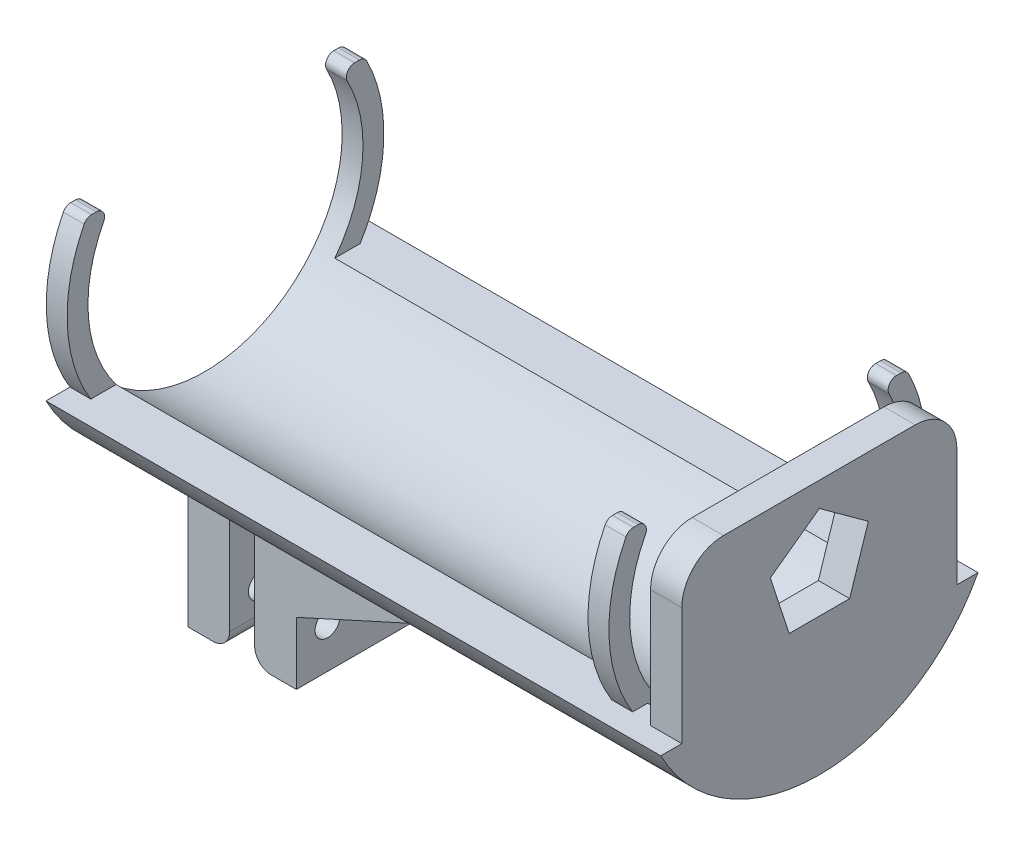
SolidWorks part; units mm, degrees
ref_plane "Front" through (0, 0, 0) normal (0, 0, 1) x (1, 0, 0)
ref_plane "Top" through (0, 0, 0) normal (0, 1, 0) x (1, 0, 0)
ref_plane "Right" through (0, 0, 0) normal (1, 0, 0) x (0, 0, -1)
sketch "Sketch1" plane through (0, 0, 0) normal (1, 0, 0) x (0, 0, -1)
  line L1 (-38.0657, -20) -> (-26.2488, -20)
  line L2 (26.2488, -20) -> (38.0657, -20)
  arc A0 (-26.2488, -20) -> (26.2488, -20) centre (0, 0) ccw
  arc A1 (-38.0657, -20) -> (38.0657, -20) centre (0, 0) ccw
  dimension "D1" = 66
  dimension "D2" = 10
  dimension "D3" = 20
extrude "Boss-Extrude1" add sketch "Sketch1" along normal mid plane 140
sketch "Sketch2" plane through (70, 0, 0) normal (1, 0, 0) x (0, 0, -1)
  line L0 (-33.3354, 18.2414) -> (-27.5, 18.2414)
  line L1 (27.5, 18.2414) -> (33.3354, 18.2414)
  arc A0 (-27.5, 18.2414) -> (27.5, 18.2414) centre (0, 0) ccw
  arc A1 (-33.3354, 18.2414) -> (33.3354, 18.2414) centre (0, 0) ccw
  dimension "D1" = 5
  dimension "D2" = 55
extrude "Boss-Extrude2" add sketch "Sketch2" against normal blind 5 from offset 5 offset against normal yes
sketch "Sketch3" plane through (70, 0, 0) normal (1, 0, 0) x (0, 0, -1)
  line L3 (-27.5, 18.2414) -> (-33.3354, 18.2414) construction
  line L4 (38.0657, -20) -> (26.2488, -20)
  line L5 (-33, -20) -> (-33, 8.2414)
  line L6 (-23, 18.2414) -> (23, 18.2414)
  line L7 (-26.2488, -20) -> (-38.0657, -20)
  line L8 (38.0657, -20) -> (33, -20)
  line L11 (-33, -20) -> (-38.0657, -20)
  line L12 (33.3354, 18.2414) -> (27.5, 18.2414) construction
  line L13 (33, 8.2414) -> (33, -20)
  arc A0 (-27.5, 18.2414) -> (-26.2488, -20) centre (0, 0) ccw construction
  arc A1 (26.2488, -20) -> (27.5, 18.2414) centre (0, 0) ccw construction
  arc A2 (23, 18.2414) -> (33, 8.2414) centre (23, 8.2414) cw
  arc A3 (-33, 8.2414) -> (-23, 18.2414) centre (-23, 8.2414) cw
  arc A5 (-26.2488, -20) -> (26.2488, -20) centre (0, 0) ccw
  arc A7 (-38.0657, -20) -> (38.0657, -20) centre (0, 0) ccw
  arc A11 (-38.0657, -20) -> (38.0657, -20) centre (0, 0) ccw
  point P24 (33, 18.2414)
  point P27 (-33, 18.2414)
  dimension "D2" = 10
  dimension "D1" = 0
extrude "Boss-Extrude3" add sketch "Sketch3" along normal blind 7.5
sketch "Sketch4" plane through (0, 0, 0) normal (0, 0, 1) x (1, 0, 0)
  line L0 (-49, -43) -> (-49, -69)
  line L1 (-70, -43) -> (77.5, -43) construction
  line L2 (-53, -73) -> (-59, -73)
  line L3 (-59, -73) -> (-59, -43)
  line L4 (-46, -43) -> (-46, -73) construction
  line L5 (-59, -43) -> (-49, -43)
  line L6 (-70, -20) -> (-70, -43) construction
  line L7 (-33, -43) -> (-43, -43)
  line L9 (-39, -73) -> (-33, -73)
  line L10 (-43, -43) -> (-43, -69)
  line L11 (-33, -58) -> (0, -43)
  line L12 (-70, -43) -> (77.5, -43) construction
  line L13 (-33, -43) -> (0, -43)
  line L14 (-33, -58) -> (-33, -73)
  arc A0 (-39, -73) -> (-43, -69) centre (-39, -69) cw
  arc A1 (-49, -69) -> (-53, -73) centre (-53, -69) cw
  point P16 (-43, -73)
  point P19 (-49, -73)
  dimension "D5" = 4
  dimension "D1" = 24
  dimension "D2" = 3
  dimension "D3" = 10
  dimension "D4" = 30
  dimension "D6" = 15
extrude "Boss-Extrude4" add sketch "Sketch4" along normal mid plane 30 separate body
sketch "Sketch5" plane through (0, -43, 0) normal (0, 1, 0) x (1, 0, 0)
  line L0 (0, 15) -> (-43, 15) construction
  line L1 (-43, 15) -> (-43, -15) construction
  line L2 (-43, -15) -> (0, -15) construction
  line L4 (-49, 15) -> (-59, 15) construction
  line L5 (-59, 15) -> (-59, -15) construction
  line L6 (-59, -15) -> (-49, -15) construction
  line L7 (-49, -15) -> (-49, 15) construction
  line L8 (0, 15) -> (-43, 15)
  line L9 (-43, 15) -> (-43, -15)
  line L10 (-43, -15) -> (0, -15)
  line L11 (0, -15) -> (0, 15)
  line L12 (-49, 15) -> (-59, 15)
  line L13 (-59, 15) -> (-59, -15)
  line L14 (-59, -15) -> (-49, -15)
  line L15 (-49, -15) -> (-49, 15)
extrude "Boss-Extrude6" add sketch "Sketch5" along normal up to surface up to face at (3.75, -31.5, 0)
sketch "Sketch6" plane through (-59, 0, 0) normal (-1, 0, 0) x (0, 0, 1)
  line L0 (0, -43) -> (0, -73) construction
  line L1 (15, -73) -> (-15, -73) construction
  arc A0 (-15, -40.2989) -> (15, -40.2989) centre (0, 0) ccw construction
  circle A1 centre (-7.5, -63) radius 3
  circle A2 centre (7.5, -63) radius 3
  dimension "D2" = 6
  dimension "D1" = 7.5
  dimension "D3" = 10
extrude "Cut-Extrude1" cut sketch "Sketch6" against normal up to surface (26 mm away) up to face at (-33, -65.5, 0)
sketch "Sketch7" plane through (70, 0, 0) normal (-1, 0, 0) x (0, 0, 1)
  circle A0 centre (0, 0) radius 35
  dimension "D1" = 70
extrude "Cut-Extrude2" cut sketch "Sketch7" along normal up to surface (5 mm away) up to face at (65, -0.9638, 32.6666)
pattern_linear "LPattern1" count 2 spacing 130 along (-1, 0, 0) of "Boss-Extrude2"
fillet "Fillet1" radius 2 8 edges at (62.5, 18.2414, 27.5) (62.5, 18.2414, -27.5) (-67.5, 18.2414, 27.5) (-67.5, 18.2414, -27.5) (62.5, 18.2414, 33.3354) (-67.5, 18.2414, 33.3354) (62.5, 18.2414, -33.3354) (-67.5, 18.2414, -33.3354)
sketch "Sketch8" plane through (70, 0, 0) normal (-1, 0, 0) x (0, 0, 1)
  line L0 (0, 0) -> (0, 12.3607) construction
  line L1 (0, 12.3607) -> (-11.7557, 3.8197)
  line L2 (-11.7557, 3.8197) -> (-7.2654, -10)
  line L3 (-7.2654, -10) -> (7.2654, -10)
  line L4 (7.2654, -10) -> (11.7557, 3.8197)
  line L5 (11.7557, 3.8197) -> (0, 12.3607)
  circle A0 centre (0, 0) radius 10 construction
  dimension "D1" = 20
extrude "Cut-Extrude3" cut sketch "Sketch8" against normal up to next
